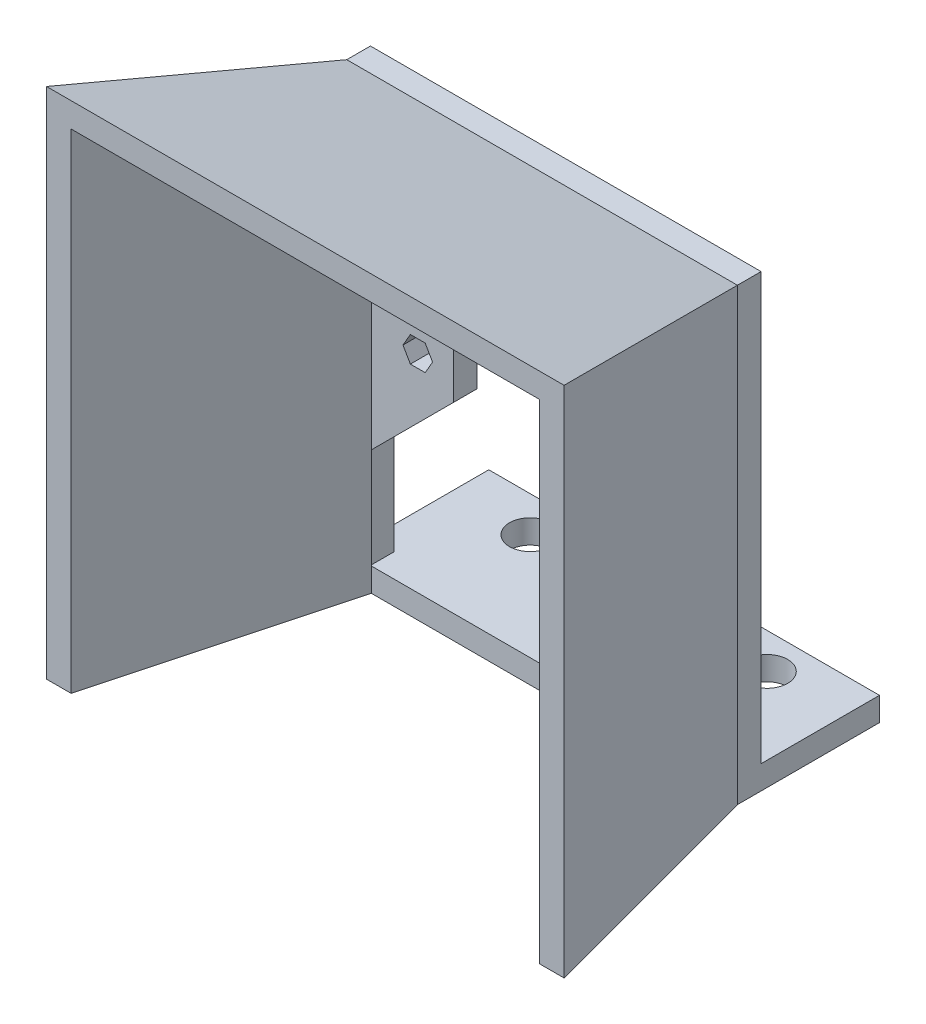
SolidWorks part; units mm, degrees
ref_plane "Front Plane" through (0, 0, 0) normal (0, 0, 1) x (1, 0, 0)
ref_plane "Top Plane" through (0, 0, 0) normal (0, 1, 0) x (1, 0, 0)
ref_plane "Right Plane" through (0, 0, 0) normal (1, 0, 0) x (0, 0, -1)
sketch "Sketch1" plane through (0, 0, 0) normal (0, 0, 1) x (1, 0, 0)
  line L0 (6, 19.5) -> (0, 19.5) construction
  line L2 (0, 0) -> (0, 38)
  line L3 (0, 38) -> (33, 38)
  line L4 (33, 0) -> (33, 38)
  line L5 (27, 19.5) -> (33, 19.5) construction
  line L7 (9, 34) -> (24, 34)
  line L8 (9, 34) -> (9, 17.4175)
  line L10 (24, 34) -> (24, 17.4175)
  line L13 (0, 0) -> (2, 0)
  line L15 (7.25, 32) -> (6.625, 33.0825)
  line L16 (6.625, 33.0825) -> (5.375, 33.0825)
  line L17 (5.375, 33.0825) -> (4.75, 32)
  line L18 (4.75, 32) -> (5.375, 30.9175)
  line L19 (5.375, 30.9175) -> (6.625, 30.9175)
  line L20 (6.625, 30.9175) -> (7.25, 32)
  line L21 (7.25, 19.5) -> (6.625, 20.5825)
  line L22 (6.625, 20.5825) -> (5.375, 20.5825)
  line L23 (5.375, 20.5825) -> (4.75, 19.5)
  line L24 (4.75, 19.5) -> (5.375, 18.4175)
  line L25 (5.375, 18.4175) -> (6.625, 18.4175)
  line L26 (6.625, 18.4175) -> (7.25, 19.5)
  line L27 (25.75, 19.5) -> (26.375, 18.4175)
  line L28 (26.375, 18.4175) -> (27.625, 18.4175)
  line L29 (27.625, 18.4175) -> (28.25, 19.5)
  line L30 (28.25, 19.5) -> (27.625, 20.5825)
  line L31 (27.625, 20.5825) -> (26.375, 20.5825)
  line L32 (26.375, 20.5825) -> (25.75, 19.5)
  line L33 (28.25, 32) -> (27.625, 33.0825)
  line L34 (27.625, 33.0825) -> (26.375, 33.0825)
  line L35 (26.375, 33.0825) -> (25.75, 32)
  line L36 (25.75, 32) -> (26.375, 30.9175)
  line L37 (26.375, 30.9175) -> (27.625, 30.9175)
  line L38 (27.625, 30.9175) -> (28.25, 32)
  line L40 (33, 0) -> (31, 0)
  line L42 (2, 0) -> (2, 10.4175)
  line L43 (2, 10.4175) -> (9, 17.4175)
  line L44 (31, 0) -> (31, 10.4175)
  line L46 (31, 10.4175) -> (24, 17.4175)
  circle A0 centre (6, 19.5) radius 1.25 construction
  circle A1 centre (27, 19.5) radius 1.25 construction
  circle A2 centre (27, 32) radius 1.25 construction
  circle A3 centre (6, 32) radius 1.25 construction
  circle A4 centre (6, 32) radius 1.0825 construction
  circle A5 centre (6, 19.5) radius 1.0825 construction
  circle A6 centre (27, 19.5) radius 1.0825 construction
  circle A7 centre (27, 32) radius 1.0825 construction
  point P13 (16.5, 34)
  point P20 (16.5, 38)
  point P53 (9, 9.5482)
  dimension "D3" = 2.5
  dimension "D1" = 33
  dimension "D2" = 38
  dimension "D4" = 21
  dimension "D5" = 12.5
  dimension "D6" = 6
  dimension "D7" = 3
  dimension "D8" = 4
  dimension "D9" = 2
  dimension "D10" = 135
  dimension "D11" = 8
extrude "Boss-Extrude1" add sketch "Sketch1" along normal blind 2
sketch "Sketch2" plane through (0, 0, 2) normal (0, 0, 1) x (1, 0, 0)
  line L7 (33, 0) -> (33, 38)
  line L8 (33, 38) -> (0, 38)
  line L9 (0, 38) -> (0, 0)
  line L10 (0, 0) -> (33, 0)
extrude "Boss-Extrude2" add sketch "Sketch2" along normal blind 20 draft 15 separate body draft outward yes
shell "Shell1" thickness 2 removed face at (16.5, -2.6795, 12) removed face at (16.5, 19, 22) removed face at (16.5, 19, 2)
sketch "Sketch3" plane through (0, 0, 0) normal (0, -1, 0) x (1, 0, 0)
  line L0 (31, 2) -> (33, 2) construction
  line L5 (30.9294, 2) -> (33, 2) construction
  line L6 (0, 2) -> (0, 0) construction
  line L9 (0, 2) -> (33, 2)
  line L10 (0, 2) -> (0, -10)
  line L11 (0, -10) -> (33, -10)
  line L12 (33, 2) -> (33, -10)
  point P6 (32.5565, 2)
  dimension "D1" = 12
extrude "Boss-Extrude3" add sketch "Sketch3" against normal blind 2
sketch "Sketch4" plane through (0, 2, 0) normal (0, 1, 0) x (1, 0, 0)
  line L0 (26.5, 7) -> (6.5, 7) construction
  line L1 (0, 10) -> (33, 10) construction
  circle A0 centre (26.5, 7) radius 1.75
  circle A1 centre (6.5, 7) radius 1.75
  point P6 (16.5, 10)
  point P7 (16.5, 7)
  dimension "D1" = 3.5
  dimension "D2" = 20
  dimension "D3" = 3
extrude "Cut-Extrude1" cut sketch "Sketch4" against normal through all
sketch "Sketch5" plane through (0, 0, 0) normal (0, -1, 0) x (1, 0, 0)
  line L0 (-5.359, 22) -> (38.359, 22)
  line L1 (-5.359, 22) -> (-5.359, 2)
  line L2 (38.359, 22) -> (38.359, 2)
  line L3 (-5.359, 2) -> (38.359, 2)
  line L5 (33, 2) -> (0, 2) construction
extrude "Cut-Extrude2" cut sketch "Sketch5" along normal through all
combine bodies "Combine1" operation type add bodies to combine 105 104
equation "\"width\"= 25mm"
equation "\"height\"= 24mm"
equation "\"wall_thickness\"= 2mm"
equation "\"D1@Sketch1\"=\"width\" + 2 * \"wall_thickness\" + 4"
equation "\"D2@Sketch1\"=\"height\" + 2 * \"wall_thickness\" + 10"
equation "\"D6@Sketch1\"=\"wall_thickness\" + 4"
equation "\"D1@Boss-Extrude1\"= \"wall_thickness\""
equation "\"D1@Boss-Extrude3\"=\"wall_thickness\""
equation "\"D1@Shell1\"= \"wall_thickness\""
equation "\"D9@Sketch1\"=\"wall_thickness\""
